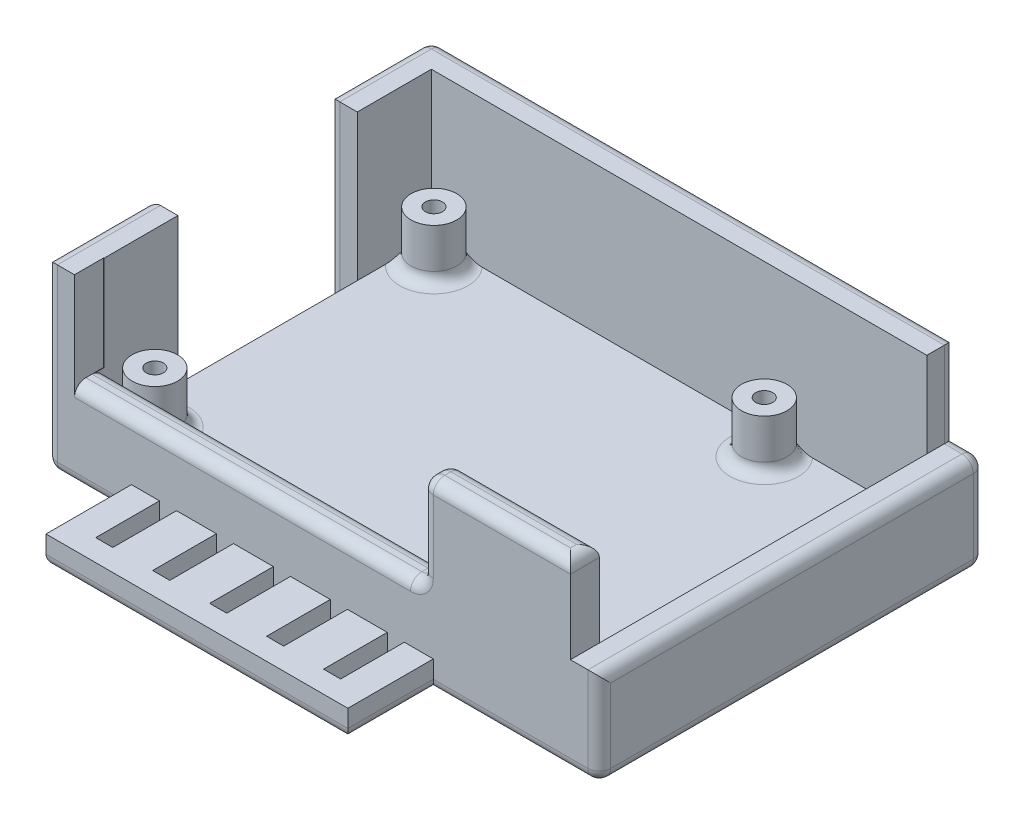
SolidWorks part; units mm, degrees
ref_plane "Front Plane" through (0, 0, 0) normal (0, 0, 1) x (1, 0, 0)
ref_plane "Top Plane" through (0, 0, 0) normal (0, 1, 0) x (1, 0, 0)
ref_plane "Right Plane" through (0, 0, 0) normal (1, 0, 0) x (0, 0, -1)
sketch "Sketch1" plane through (0, 0, 0) normal (0, 1, 0) x (1, 0, 0)
  line L1 (-46.4499, -22.2302) -> (40.5501, -22.2302)
  line L2 (-46.4499, -22.2302) -> (-46.4499, 35.2698)
  line L3 (-46.4499, 35.2698) -> (40.5501, 35.2698)
  line L4 (40.5501, -22.2302) -> (40.5501, 35.2698)
  dimension "D1" = 87
  dimension "D2" = 57.5
extrude "Boss-Extrude1" add sketch "Sketch1" along normal blind 6.35
sketch "Sketch2" plane through (0, 6.35, 0) normal (0, 1, 0) x (1, 0, 0)
  line L0 (40.5501, 35.2698) -> (-46.4499, 35.2698) construction
  line L1 (-46.4499, 35.2698) -> (-46.4499, -22.2302) construction
  circle A0 centre (-41.9499, 31.2198) radius 4
  circle A2 centre (16.0501, 31.2198) radius 4
  circle A3 centre (16.0501, -17.7802) radius 4
  circle A4 centre (-41.9499, -17.7802) radius 4
  dimension "D5" = 8
  dimension "D1" = 4.05
  dimension "D2" = 4.5
  dimension "D3" = 2
  dimension "D4" = 2
extrude "Boss-Extrude2" add sketch "Sketch2" along normal blind 9
sketch "Sketch3" plane through (0, 15.35, 0) normal (0, 1, 0) x (1, 0, 0)
  circle A0 centre (-41.9499, 31.2198) radius 1.5
  circle A1 centre (16.0501, 31.2198) radius 1.5
  circle A2 centre (16.0501, -17.7802) radius 1.5
  circle A3 centre (-41.9499, -17.7802) radius 1.5
  dimension "D3" = 3
  dimension "D1" = 2
  dimension "D2" = 2
extrude "Cut-Extrude1" cut sketch "Sketch3" against normal up to surface (15.35 mm away) up to face at (-2.9499, 0, -6.5198)
sketch "Sketch4" plane through (-46.4499, 0, 0) normal (-1, 0, 0) x (0, 0, 1)
  line L1 (-35.2698, 0) -> (-22.2698, 0)
  line L2 (-35.2698, 0) -> (-35.2698, 32)
  line L3 (-35.2698, 32) -> (-22.2698, 32)
  line L4 (-22.2698, 0) -> (-22.2698, 32)
  line L5 (22.2302, 0) -> (9.2302, 0)
  line L6 (22.2302, 0) -> (22.2302, 32)
  line L7 (22.2302, 32) -> (9.2302, 32)
  line L8 (9.2302, 0) -> (9.2302, 32)
  dimension "D1" = 13
  dimension "D2" = 13
  dimension "D3" = 32
extrude "Boss-Extrude3" add sketch "Sketch4" along normal blind 5.08
sketch "Sketch5" plane through (0, 0, -35.2698) normal (0, 0, -1) x (-1, 0, 0)
  line L0 (51.5299, 32) -> (46.4499, 32) construction
  line L1 (51.5299, 0) -> (-40.5501, 0)
  line L2 (51.5299, 0) -> (51.5299, 32)
  line L3 (51.5299, 32) -> (-40.5501, 32)
  line L4 (-40.5501, 0) -> (-40.5501, 32)
  line L5 (-40.5501, 6.35) -> (-40.5501, 0) construction
extrude "Boss-Extrude4" add sketch "Sketch5" along normal blind 5.08
sketch "Sketch6" plane through (0, 0, 22.2302) normal (0, 0, 1) x (1, 0, 0)
  line L0 (-51.5299, 32) -> (-46.4499, 32) construction
  line L1 (-51.5299, 0) -> (-46.5299, 0)
  line L2 (-51.5299, 0) -> (-51.5299, 32)
  line L3 (-51.5299, 32) -> (-46.5299, 32)
  line L4 (-46.5299, 0) -> (-46.5299, 32)
  dimension "D1" = 5
extrude "Boss-Extrude5" add sketch "Sketch6" along normal blind 5.08
sketch "Sketch7" plane through (0, 0, 22.2302) normal (0, 0, 1) x (1, 0, 0)
  line L0 (-37.9499, 15.35) -> (-45.9499, 15.35) construction
  line L1 (-46.5299, 0) -> (21.4701, 0)
  line L2 (-46.5299, 0) -> (-46.5299, 15.35)
  line L3 (-46.5299, 15.35) -> (21.4701, 15.35)
  line L4 (21.4701, 0) -> (21.4701, 15.35)
  dimension "D1" = 68
extrude "Boss-Extrude6" add sketch "Sketch7" along normal blind 5.08
sketch "Sketch8" plane through (0, 0, 22.2302) normal (0, 0, 1) x (1, 0, 0)
  line L1 (21.4701, 0) -> (40.5501, 0)
  line L2 (21.4701, 0) -> (21.4701, 32)
  line L3 (21.4701, 32) -> (40.5501, 32)
  line L4 (40.5501, 0) -> (40.5501, 32)
  line L5 (40.5501, 6.35) -> (40.5501, 0) construction
  line L6 (-46.4499, 32) -> (40.5501, 32) construction
extrude "Boss-Extrude7" add sketch "Sketch8" along normal blind 5.08
sketch "Sketch9" plane through (40.5501, 0, 0) normal (1, 0, 0) x (0, 0, -1)
  line L1 (-27.3102, 0) -> (40.3498, 0)
  line L2 (-27.3102, 0) -> (-27.3102, 17)
  line L3 (-27.3102, 17) -> (40.3498, 17)
  line L4 (40.3498, 0) -> (40.3498, 17)
  line L5 (40.3498, 32) -> (40.3498, 0) construction
  dimension "D1" = 17
extrude "Boss-Extrude8" add sketch "Sketch9" along normal blind 5.08
sketch "Sketch10" plane through (0, 0, 0) normal (0, -1, 0) x (1, 0, 0)
  line L1 (33.4701, -19.3498) -> (-36.5299, -19.3498)
  line L2 (33.4701, -19.3498) -> (33.4701, -24.4298)
  line L3 (33.4701, -24.4298) -> (-36.5299, -24.4298)
  line L4 (-36.5299, -19.3498) -> (-36.5299, -24.4298)
  dimension "D3" = 70
extrude "Boss-Extrude9" add sketch "Sketch10" along normal blind 4
sketch "Sketch11" plane through (0, -4, 0) normal (0, -1, 0) x (1, 0, 0)
  line L0 (-36.5299, -19.3498) -> (-36.5299, -24.4298) construction
  line L1 (33.4701, -24.4298) -> (-36.5299, -24.4298)
  line L2 (33.4701, -24.4298) -> (33.4701, -14.4298)
  line L3 (33.4701, -14.4298) -> (-36.5299, -14.4298)
  line L4 (-36.5299, -24.4298) -> (-36.5299, -14.4298)
  dimension "D1" = 10
extrude "Boss-Extrude10" add sketch "Sketch11" along normal blind 5.08
fillet "Fillet2" radius 1 18 edges at (33.4701, 0, -21.8898) (33.4701, -2, -19.3498) (-1.5299, 0, -19.3498) (-1.5299, -4, -19.3498) (33.4701, -4, -16.8898) (33.4701, -6.54, -14.4298) (-1.5299, -4, -14.4298) (-1.5299, -9.08, -14.4298) (33.4701, -9.08, -19.4298) (-36.5299, -2, -19.3498) (-36.5299, -4, -16.8898) (-36.5299, -6.54, -14.4298) (-36.5299, -9.08, -19.4298) (-36.5299, 0, -21.8898) (-36.5299, -4.54, -24.4298) (-1.5299, -9.08, -24.4298) (33.4701, -4.54, -24.4298) (-1.5299, 0, -24.4298)
sketch "Sketch13" plane through (0, 0, 27.3102) normal (0, 0, 1) x (1, 0, 0)
  line L1 (16.4701, 0) -> (-36.5299, 0)
  line L2 (16.4701, 0) -> (16.4701, 5.08)
  line L3 (16.4701, 5.08) -> (-36.5299, 5.08)
  line L4 (-36.5299, 0) -> (-36.5299, 5.08)
  line L7 (-46.5299, 15.35) -> (-46.5299, 32) construction
  line L8 (21.4701, 32) -> (21.4701, 15.35) construction
  dimension "D1" = 5.08
  dimension "D2" = 10
  dimension "D3" = 5
extrude "Boss-Extrude11" add sketch "Sketch13" along normal blind 15
sketch "Sketch14" plane through (0, 5.08, 0) normal (0, 1, 0) x (1, 0, 0)
  line L0 (16.4701, -27.3102) -> (-36.5299, -27.3102) construction
  line L1 (11.3901, -27.3102) -> (8.3901, -27.3102)
  line L2 (11.3901, -27.3102) -> (11.3901, -38.5002)
  line L3 (11.3901, -38.5002) -> (8.3901, -38.5002)
  line L4 (8.3901, -27.3102) -> (8.3901, -38.5002)
  line L6 (16.4701, -42.3102) -> (16.4701, -27.3102) construction
  line L7 (16.4701, -42.3102) -> (-36.5299, -42.3102) construction
  line L8 (1.3901, -27.3102) -> (1.3901, -38.5002)
  line L9 (1.3901, -27.3102) -> (-1.6099, -27.3102)
  line L10 (-1.6099, -27.3102) -> (-1.6099, -38.5002)
  line L11 (1.3901, -38.5002) -> (-1.6099, -38.5002)
  line L12 (-8.6099, -27.3102) -> (-8.6099, -38.5002)
  line L13 (-8.6099, -27.3102) -> (-11.6099, -27.3102)
  line L14 (-11.6099, -27.3102) -> (-11.6099, -38.5002)
  line L15 (-8.6099, -38.5002) -> (-11.6099, -38.5002)
  line L16 (-18.6099, -27.3102) -> (-18.6099, -38.5002)
  line L17 (-18.6099, -27.3102) -> (-21.6099, -27.3102)
  line L18 (-21.6099, -27.3102) -> (-21.6099, -38.5002)
  line L19 (-18.6099, -38.5002) -> (-21.6099, -38.5002)
  line L20 (-28.6099, -27.3102) -> (-28.6099, -38.5002)
  line L21 (-28.6099, -27.3102) -> (-31.6099, -27.3102)
  line L22 (-31.6099, -27.3102) -> (-31.6099, -38.5002)
  line L23 (-28.6099, -38.5002) -> (-31.6099, -38.5002)
  dimension "D1" = 5.08
  dimension "D2" = 3
  dimension "D3" = 3.81
  dimension "D4" = 5
extrude "Cut-Extrude2" cut sketch "Sketch14" against normal blind 15
sketch "Sketch15" plane through (0, 0, 0) normal (0, -1, 0) x (-1, 0, 0)
  circle A0 centre (41.9499, 31.2198) radius 2.5
  circle A1 centre (-16.0501, 31.2198) radius 2.5
  circle A2 centre (-16.0501, -17.7802) radius 2.5
  circle A3 centre (41.9499, -17.7802) radius 2.5
  dimension "D1" = 5
  dimension "D2" = 2
  dimension "D3" = 2
extrude "Cut-Extrude3" cut sketch "Sketch15" against normal blind 3.5
sketch "Sketch16" plane through (21.4701, 0, 0) normal (-1, 0, 0) x (0, 0, 1)
  line L0 (27.3102, 32) -> (27.3102, 15.35) construction
  line L1 (22.2302, 32) -> (27.3102, 32)
  line L2 (22.2302, 32) -> (22.2302, 15.35)
  line L3 (22.2302, 15.35) -> (27.3102, 15.35)
  line L4 (27.3102, 32) -> (27.3102, 15.35)
extrude "Boss-Extrude12" add sketch "Sketch16" along normal blind 7
fillet "Fillet3" radius 2 61 edges at (-16.0299, 15.35, 27.3102) (-15.9899, 15.35, 22.2302) (14.4701, 23.675, 27.3102) (14.4701, 15.35, 24.7702) (14.4701, 23.675, 22.2302) (40.5501, 32, 24.7702) (27.5101, 32, 27.3102) (14.4701, 32, 24.7702) (27.5101, 32, 22.2302) (45.6301, 17, -6.5198) (45.6301, 8.5, 27.3102) (-48.9899, 0, -22.2698) (-46.4499, 0, -6.5198) (-48.9899, 0, 9.2302) (-44.0299, 0, 27.3102) (-36.5299, 0, 34.8102) (-10.0299, 0, 42.3102) (16.4701, 0, 34.8102) (31.0501, 0, 27.3102) (45.6301, 0, -6.5198) (-28.6099, 0, 32.9052) (-30.1099, 0, 38.5002) (-31.6099, 0, 32.9052) (-30.1099, 0, 27.3102) (-18.6099, 0, 32.9052) (-20.1099, 0, 38.5002) (-21.6099, 0, 32.9052) (-20.1099, 0, 27.3102) (-8.6099, 0, 32.9052) (-10.1099, 0, 38.5002) (-11.6099, 0, 32.9052) (-10.1099, 0, 27.3102) (1.3901, 0, 32.9052) (-0.1099, 0, 38.5002) (-1.6099, 0, 32.9052) (-0.1099, 0, 27.3102) (9.8901, 0, 38.5002) (8.3901, 0, 32.9052) (9.8901, 0, 27.3102) (11.3901, 0, 32.9052) (-41.9499, 0, -33.7198) (16.0501, 0, -33.7198) (16.0501, 0, 15.2802) (-41.9499, 0, 15.2802) (-2.9499, 0, -40.3498) (45.6301, 8.5, -40.3498) (43.0901, 17, -40.3498) (40.5501, 24.5, -40.3498) (-5.4899, 32, -40.3498) (-51.5299, 16, -22.2698) (-51.5299, 0, -31.3098) (-51.5299, 16, -40.3498) (-51.5299, 32, -31.3098) (-51.5299, 16, 9.2302) (-51.5299, 32, 18.2702) (-51.5299, 16, 27.3102) (-51.5299, 0, 18.2702) (16.0501, 6.35, 13.7802) (16.0501, 6.35, -35.2198) (-41.9499, 6.35, 13.7802) (-41.9499, 6.35, -35.2198)
